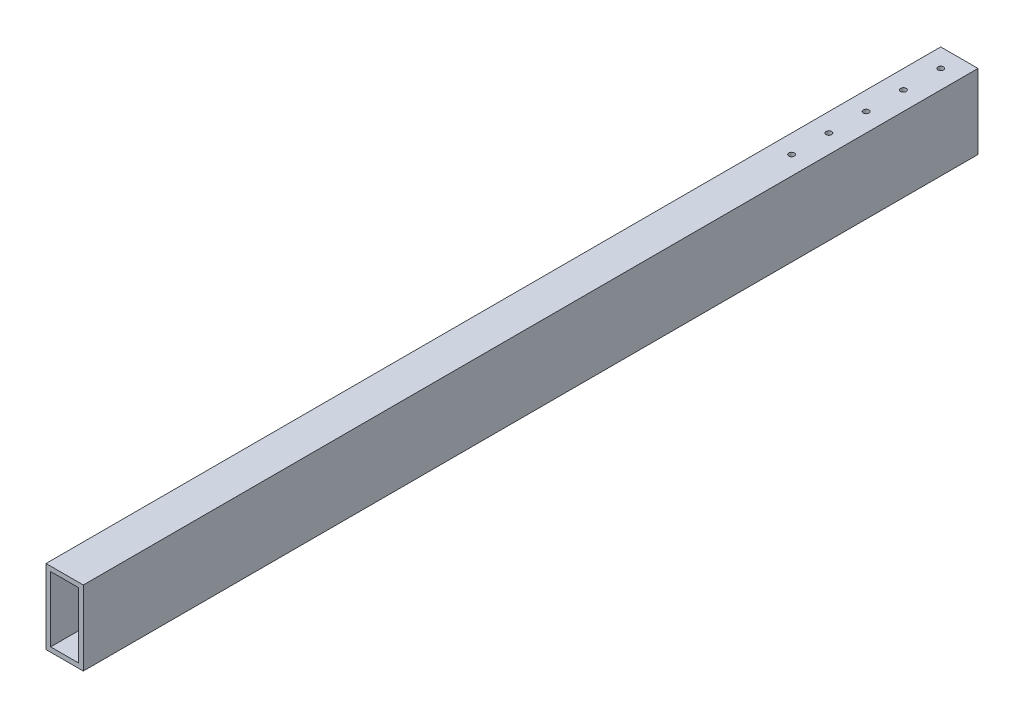
SolidWorks part; units mm, degrees
material "6061-T6 (SS)"
ref_plane "Front Plane" through (0, 0, 0) normal (0, 0, 1) x (1, 0, 0)
ref_plane "Top Plane" through (0, 0, 0) normal (0, 1, 0) x (1, 0, 0)
ref_plane "Right Plane" through (0, 0, 0) normal (1, 0, 0) x (0, 0, -1)
sketch "Sketch1" plane through (0, 0, 0) normal (0, 0, 1) x (1, 0, 0)
  line L0 (-9.525, 22.225) -> (9.525, 22.225)
  line L1 (-12.7, 25.4) -> (12.7, 25.4)
  line L2 (-12.7, 25.4) -> (-12.7, -25.4)
  line L3 (-12.7, -25.4) -> (12.7, -25.4)
  line L4 (12.7, 25.4) -> (12.7, -25.4)
  line L5 (-12.7, 25.4) -> (12.7, -25.4) construction
  line L6 (-12.7, -25.4) -> (12.7, 25.4) construction
  line L7 (9.525, 22.225) -> (9.525, -22.225)
  line L8 (-9.525, -22.225) -> (9.525, -22.225)
  line L9 (-9.525, 22.225) -> (-9.525, -22.225)
  point P0 (0, 0)
  dimension "D1" = 50.8
  dimension "D2" = 25.4
  dimension "D3" = 3.175
extrude "Boss-Extrude1" add sketch "Sketch1" along normal mid plane 609.6
sketch "Sketch7" plane through (0, 25.4, 0) normal (0, 1, 0) x (1, 0, 0)
  line L0 (-12.7, -304.8) -> (-12.7, 304.8) construction
  line L1 (12.7, 304.8) -> (-12.7, 304.8) construction
  circle A0 centre (0, 292.1) radius 1.905
  circle A1 centre (0, 266.7) radius 1.905
  circle A2 centre (0, 241.3) radius 1.905
  circle A3 centre (0, 215.9) radius 1.905
  circle A4 centre (0, 190.5) radius 1.905
  dimension "D1" = 3.81
  dimension "D2" = 12.7
  dimension "D3" = 12.7
  dimension "D4" = 5
extrude "Cut-Extrude1" cut sketch "Sketch7" against normal through all
